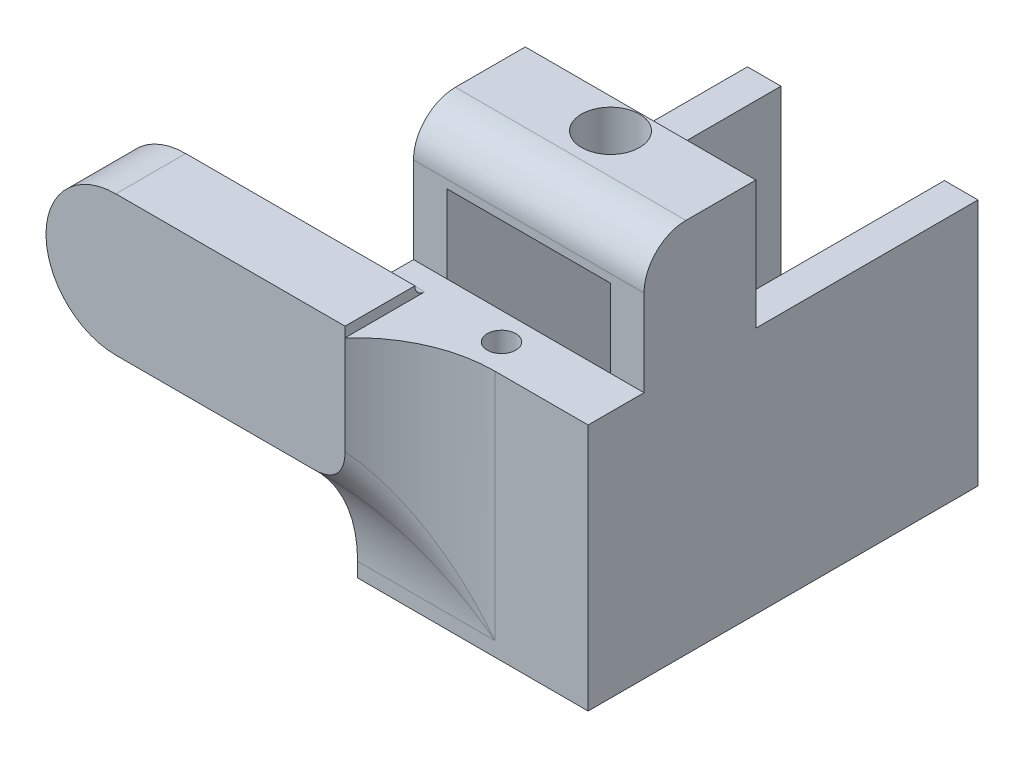
SolidWorks part; units mm, degrees
ref_plane "Front" through (0, 0, 0) normal (0, 0, 1) x (1, 0, 0)
ref_plane "Top" through (0, 0, 0) normal (0, 1, 0) x (1, 0, 0)
ref_plane "Right" through (0, 0, 0) normal (1, 0, 0) x (0, 0, -1)
sketch "Sketch1" plane through (0, 0, 0) normal (0, 1, 0) x (1, 0, 0)
  line L22 (-5.75, -16) -> (5.75, -16) construction
  line L23 (8.25, -16) -> (-8.25, -16)
  line L25 (8.25, -16) -> (8.25, 11.9)
  line L26 (8.25, 11.9) -> (-8.25, 11.9)
  line L27 (-8.25, -16) -> (-8.25, 11.9)
  line L28 (5.75, 11.9) -> (-5.75, 11.9) construction
  line L29 (0, -16) -> (0, 11.9) construction
  line L30 (5.75, -11.9) -> (5.75, 11.9) construction
  dimension "D1" = 2.5
extrude "Boss-Extrude1" add sketch "Sketch1" against normal blind 3 contours L25 L23 L27 L26
sketch "Sketch3" plane through (0, 0, 0) normal (0, 1, 0) x (1, 0, 0)
  line L0 (8.25, 11.9) -> (-8.25, 11.9) construction
  line L1 (-5.85, 11.9) -> (-8.25, 11.9)
  line L2 (-8.25, 11.9) -> (-8.25, -16)
  line L3 (-8.25, -16) -> (8.25, -16)
  line L4 (8.25, -16) -> (8.25, 11.9)
  line L5 (8.25, 11.9) -> (5.85, 11.9)
  line L8 (-5.85, -12) -> (5.85, -12)
  line L9 (-5.85, 12) -> (-5.85, -12)
  line L10 (5.85, 12) -> (-5.85, 12)
  line L11 (5.85, -12) -> (5.85, 12)
  line L12 (-5.85, -12) -> (5.85, -12)
  line L13 (-5.85, 11.9) -> (-5.85, -12)
  line L15 (5.85, -12) -> (5.85, 11.9)
  dimension "D1" = 0.1
extrude "Boss-Extrude3" add sketch "Sketch3" along normal up to surface (14.732 mm away)
sketch "Sketch5" plane through (0, 14.732, 0) normal (0, 1, 0) x (1, 0, 0)
  circle A4 centre (0, -13.95) radius 1.025
  circle A5 centre (0, -13.95) radius 1.025
  dimension "D1" = 0.1
extrude "Cut-Extrude1" cut sketch "Sketch5" against normal blind 8 contours A5
sketch "PivotLocations" plane through (0, 0, 0) normal (1, 0, 0) x (0, 0, -1)
  line L0 (8.065, 27.2415) -> (4.235, 27.2415) construction
  line L1 (8.065, 27.2415) -> (4.235, 27.2415) construction
  line L2 (0, 0) -> (0, 30.9576) construction
  line L3 (6.15, 27.2415) -> (6.15, 0)
  line L4 (0, 0) -> (6.15, 0) construction
  line L5 (-6.15, 27.2415) -> (-6.15, 0)
  point P6 (6.15, 27.2415)
sketch "Sketch8" plane through (0, -3, 0) normal (0, -1, 0) x (1, 0, 0)
  circle A0 centre (0, 6.15) radius 2.075
  circle A1 centre (0, -6.15) radius 2.075
  point P0 (0, -6.15)
  point P2 (0, 6.15)
  dimension "D1" = 4.15
extrude "Cut-Extrude2" cut sketch "Sketch8" against normal blind 3
sketch "Sketch9" plane through (0, 14.732, 0) normal (0, 1, 0) x (1, 0, 0)
  line L0 (-8.25, -16) -> (-8.25, 11.9) construction
  line L1 (-5.85, -12) -> (-8.25, -12)
  line L2 (-5.85, -12) -> (-5.85, -4)
  line L3 (-5.85, -4) -> (-8.25, -4)
  line L4 (-8.25, -12) -> (-8.25, -4)
  line L5 (8.25, 11.9) -> (8.25, -16) construction
  line L6 (5.85, -12) -> (8.25, -12)
  line L7 (5.85, -12) -> (5.85, -4)
  line L8 (5.85, -4) -> (8.25, -4)
  line L9 (8.25, -12) -> (8.25, -4)
  circle A0 centre (0, -6.15) radius 2.15 construction
  point P14 (0, -6.15)
  dimension "D1" = 8
extrude "Boss-Extrude4" add sketch "Sketch9" along normal up to surface (5.588 mm away)
sketch "Sketch10" plane through (0, 20.32, 0) normal (0, 1, 0) x (1, 0, 0)
  line L1 (-8.25, -4) -> (8.25, -4)
  line L2 (-8.25, -4) -> (-8.25, -12)
  line L3 (-8.25, -12) -> (8.25, -12)
  line L4 (8.25, -4) -> (8.25, -12)
extrude "Boss-Extrude5" add sketch "Sketch10" along normal up to surface (3.5941 mm away) contours L1 L4 L3 L2 up to face at (7.05, 14.732, -3.95)
sketch "Sketch11" plane through (0, 23.9141, 0) normal (0, 1, 0) x (1, 0, 0)
  circle A0 centre (0, -6.15) radius 2.075
  point P0 (0, -6.15)
  dimension "D1" = 4.15
extrude "Cut-Extrude5" cut sketch "Sketch11" against normal blind 3
ref_plane "Wrist Interface Plane" through (0, 0, 14.3) normal (0, 0, 1) x (1, 0, 0)
sketch "Sketch13" plane through (0, 0, 14.3) normal (0, 0, 1) x (1, 0, 0)
  line L0 (-8.25, 23.9141) -> (-8.25, -3) construction
  line L1 (8.25, -3) -> (-8.25, -3) construction
  line L2 (-8.25, 10.4571) -> (-22.25, 10.4571) construction
  line L3 (-22.25, 15.4571) -> (-8.25, 15.4571)
  line L4 (-22.25, 5.4571) -> (-8.25, 5.4571)
  line L5 (-8.25, 15.4571) -> (-5.85, 15.4571)
  line L6 (-5.85, 20.32) -> (-5.85, 14.732) construction
  line L7 (-5.85, 15.4571) -> (-5.85, 5.4571)
  line L8 (-8.25, 5.4571) -> (-5.85, 5.4571)
  line L9 (-24.485, 9.7309) -> (-24.1512, 9.0758)
  line L10 (-22.25, 12.8071) -> (-22.9762, 12.692)
  line L11 (-22.9762, 12.692) -> (-23.6313, 12.3582)
  line L12 (-23.6313, 12.3582) -> (-24.1512, 11.8383)
  line L13 (-24.1512, 11.8383) -> (-24.485, 11.1832)
  line L14 (-24.485, 11.1832) -> (-24.6, 10.4571)
  line L15 (-24.6, 10.4571) -> (-24.485, 9.7309)
  line L16 (-24.1512, 9.0758) -> (-23.6313, 8.5559)
  line L17 (-23.6313, 8.5559) -> (-22.9762, 8.2221)
  line L18 (-22.9762, 8.2221) -> (-22.25, 8.1071)
  line L19 (-22.25, 8.1071) -> (-21.5238, 8.2221)
  line L20 (-21.5238, 8.2221) -> (-20.8687, 8.5559)
  line L21 (-20.8687, 8.5559) -> (-20.3488, 9.0758)
  line L22 (-20.3488, 9.0758) -> (-20.015, 9.7309)
  line L23 (-20.015, 9.7309) -> (-19.9, 10.4571)
  line L24 (-19.9, 10.4571) -> (-20.015, 11.1832)
  line L25 (-20.015, 11.1832) -> (-20.3488, 11.8383)
  line L26 (-20.3488, 11.8383) -> (-20.8687, 12.3582)
  line L27 (-20.8687, 12.3582) -> (-21.5238, 12.692)
  line L28 (-21.5238, 12.692) -> (-22.25, 12.8071)
  circle A0 centre (-22.25, 10.4571) radius 2.35 construction
  arc A1 (-22.25, 15.4571) -> (-22.25, 5.4571) centre (-22.25, 10.4571) ccw
  circle A2 centre (-22.25, 10.4571) radius 2.3211 construction
  dimension "D1" = 14
  dimension "D2" = 4.7
  dimension "D3" = 5
extrude "Boss-Extrude6" add sketch "Sketch13" along normal blind 3 contours L3 A1 L4 L8 L7 L5 L28 L27 L26 L25 L24 L23 L22 L21 L20 L19 L18 L17 L16 L9 L15 L14 L13 L12 L11 L10 region at (-15.4754, 10.4571, 14.3)
sketch "Sketch14" plane through (0, 0, 17.3) normal (0, 0, 1) x (1, 0, 0)
  line L3 (-5.85, 15.4571) -> (-22.25, 15.4571)
  line L4 (-22.25, 5.4571) -> (-5.85, 5.4571)
  line L5 (-5.85, 5.4571) -> (-5.85, 15.4571)
  line L6 (-5.85, 15.4571) -> (-22.25, 15.4571)
  line L7 (-22.25, 5.4571) -> (-5.85, 5.4571)
  line L8 (-5.85, 5.4571) -> (-5.85, 15.4571)
  arc A1 (-22.25, 15.4571) -> (-22.25, 5.4571) centre (-22.25, 10.4571) ccw
  arc A2 (-22.25, 15.4571) -> (-22.25, 5.4571) centre (-22.25, 10.4571) ccw
  dimension "D1" = 0
extrude "Boss-Extrude7" add sketch "Sketch14" along normal blind 2
fillet "Fillet1" radius 10 2 edges at (-7.05, 5.4571, 16) (-5.85, 10.0945, 16)
fillet "Fillet2" radius 0.7 1 edges at (-7.05, 14.732, 14.3)
fillet "Fillet3" radius 3 1 edges at (0, 23.9141, 12)
fillet "Fillet4" radius 3 1 edges at (-2.4884, 2.0955, 16.8622)
